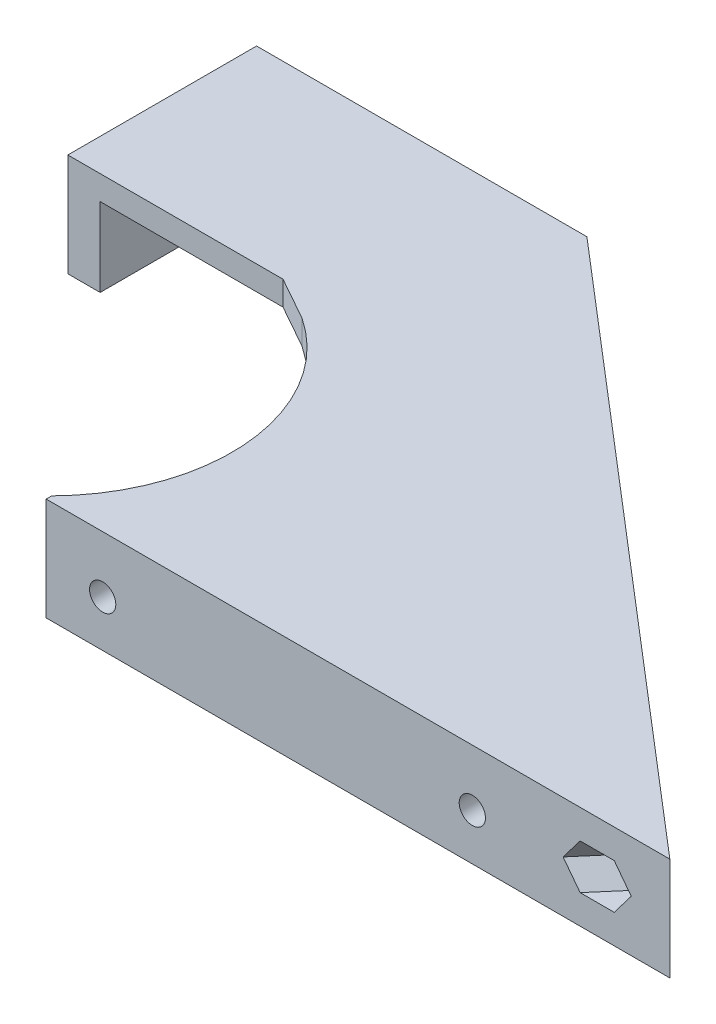
SolidWorks part; units mm, degrees
ref_plane "Alzado" through (0, 0, 0) normal (0, 0, 1) x (1, 0, 0)
ref_plane "Planta" through (0, 0, 0) normal (0, 1, 0) x (1, 0, 0)
ref_plane "Vista lateral" through (0, 0, 0) normal (1, 0, 0) x (0, 0, -1)
sketch "Croquis1" plane through (0, 0, 0) normal (0, 1, 0) x (1, 0, 0)
  line L0 (0, 0) -> (72.7832, 0)
  line L1 (72.7832, 0) -> (38.2245, 29.6204)
  line L2 (38.2245, 29.6204) -> (35.6214, 26.5833)
  line L3 (35.6214, 26.5833) -> (60.8031, 5)
  line L4 (60.8031, 5) -> (0, 5)
  line L5 (0, 5) -> (0, 0)
  dimension "D1" = 4
  dimension "D2" = 5
  dimension "D3" = 40.6
  dimension "D4" = 72.7832
extrude "Saliente-Extruir1" add sketch "Croquis1" along normal blind 12.75
sketch "Croquis2" plane through (0, 0, 0) normal (0, 0, 1) x (1, 0, 0)
  line L2 (0, 12.75) -> (72.7832, 12.75) construction
  line L3 (72.7832, 12.75) -> (72.7832, 0) construction
  circle A0 centre (52.7832, 5.75) radius 1.625
  circle A1 centre (7, 5.75) radius 1.625
  dimension "D1" = 3.25
  dimension "D2" = 20
  dimension "D3" = 7
  dimension "D4" = 45.7832
  dimension "D5" = 7
extrude "Cortar-Extruir1" cut sketch "Croquis2" against normal up to next
sketch "Croquis3" plane through (0, 12.75, 0) normal (0, 1, 0) x (1, 0, 0)
  line L0 (0, 5) -> (0, 0) construction
  line L1 (0, 0) -> (72.7832, 0) construction
  circle A0 centre (-16, 16.5) radius 22.5
  dimension "D1" = 45
  dimension "D2" = 16
  dimension "D3" = 16.5
extrude "Cortar-Extruir2" cut sketch "Croquis3" against normal through all
sketch "Croquis4" plane through (0, 12.75, 0) normal (0, 1, 0) x (1, 0, 0)
  line L0 (38.2245, 29.6204) -> (31.6563, 35.25)
  line L1 (31.6563, 35.25) -> (-3.5627, 35.25)
  line L2 (0, 0) -> (72.7832, 0) construction
  line L3 (72.7832, 0) -> (38.2245, 29.6204) construction
  line L4 (38.2245, 29.6204) -> (35.6214, 26.5833)
  line L5 (35.6214, 26.5833) -> (60.8031, 5)
  line L6 (60.8031, 5) -> (3.3391, 5)
  arc A0 (3.3391, 5) -> (-3.5627, 35.25) centre (-16, 16.5) ccw
  arc A1 (0, 0.6807) -> (3.3391, 5) centre (-16, 16.5) ccw construction
  dimension "D1" = 35.25
extrude "Saliente-Extruir2" add sketch "Croquis4" against normal blind 3
sketch "Croquis5" plane through (0, 9.75, 0) normal (0, -1, 0) x (1, 0, 0)
  line L0 (-3.5627, -35.25) -> (31.6563, -35.25)
  line L1 (31.6563, -35.25) -> (38.2245, -29.6204)
  line L2 (38.2245, -29.6204) -> (35.6214, -26.5833)
  line L3 (35.6214, -26.5833) -> (30.1767, -31.25)
  line L4 (30.1767, -31.25) -> (0.9908, -31.25)
  arc A0 (-3.5627, -35.25) -> (3.3391, -5) centre (-16, -16.5) ccw construction
  arc A1 (-3.5627, -35.25) -> (0.9908, -31.25) centre (-16, -16.5) ccw
  dimension "D1" = 4
extrude "Saliente-Extruir3" add sketch "Croquis5" along normal up to vertex (9.75 mm away) up to point (38.2245, 0, -29.6204)
sketch "Croquis6" plane through (30.8242, 0, -35.9632) normal (0.6508, 0, -0.7593) x (-0.7593, 0, -0.6508)
  line L0 (-55.2622, 12.75) -> (-55.2622, 0) construction
  line L1 (-1.0959, 0) -> (-1.0959, 12.75) construction
  circle A0 centre (-47.2622, 6.375) radius 1.625
  circle A1 centre (-16.0959, 6.375) radius 1.625
  dimension "D1" = 3.25
  dimension "D2" = 3.25
  dimension "D3" = 8
  dimension "D4" = 15
extrude "Cortar-Extruir3" cut sketch "Croquis6" against normal blind 10
sketch "Croquis7" plane through (28.2211, 0, -32.9261) normal (-0.6508, 0, 0.7593) x (0.7593, 0, 0.6508)
  line L1 (48.8499, 3.625) -> (50.4376, 6.375)
  line L2 (50.4376, 6.375) -> (48.8499, 9.125)
  line L3 (48.8499, 9.125) -> (45.6745, 9.125)
  line L4 (45.6745, 9.125) -> (44.0868, 6.375)
  line L5 (44.0868, 6.375) -> (45.6745, 3.625)
  line L6 (45.6745, 3.625) -> (48.8499, 3.625)
  circle A0 centre (47.2622, 6.375) radius 2.75 construction
  dimension "D1" = 5.5
extrude "Cortar-Extruir4" cut sketch "Croquis7" along normal blind 10 from offset 2 offset against normal yes
sketch "Croquis8" plane through (28.2211, 0, -32.9261) normal (-0.6508, 0, 0.7593) x (0.7593, 0, 0.6508)
  line L0 (45.6745, 3.625) -> (48.8499, 3.625) construction
  line L1 (17.6837, 3.625) -> (19.2714, 6.375)
  line L2 (19.2714, 6.375) -> (17.6837, 9.125)
  line L3 (17.6837, 9.125) -> (14.5082, 9.125)
  line L4 (14.5082, 9.125) -> (12.9205, 6.375)
  line L5 (12.9205, 6.375) -> (14.5082, 3.625)
  line L6 (14.5082, 3.625) -> (17.6837, 3.625)
  circle A0 centre (16.0959, 6.375) radius 2.75 construction
extrude "Cortar-Extruir5" cut sketch "Croquis8" along normal blind 10 from offset 2 offset against normal yes
sketch "Croquis9" plane through (0, 0, -5) normal (0, 0, -1) x (-1, 0, 0)
  line L1 (-5.4123, 3) -> (-3.8246, 5.75)
  line L2 (-3.8246, 5.75) -> (-5.4123, 8.5)
  line L3 (-5.4123, 8.5) -> (-8.5877, 8.5)
  line L4 (-8.5877, 8.5) -> (-10.1754, 5.75)
  line L5 (-10.1754, 5.75) -> (-8.5877, 3)
  line L6 (-8.5877, 3) -> (-5.4123, 3)
  line L7 (-51.1955, 3) -> (-49.6078, 5.75)
  line L8 (-49.6078, 5.75) -> (-51.1955, 8.5)
  line L9 (-51.1955, 8.5) -> (-54.3709, 8.5)
  line L10 (-54.3709, 8.5) -> (-55.9586, 5.75)
  line L11 (-55.9586, 5.75) -> (-54.3709, 3)
  line L12 (-54.3709, 3) -> (-51.1955, 3)
  circle A0 centre (-7, 5.75) radius 2.75 construction
  circle A1 centre (-52.7832, 5.75) radius 2.75 construction
  dimension "D1" = 5.5
extrude "Cortar-Extruir6" cut sketch "Croquis9" against normal blind 2
sketch "Croquis10" plane through (0, 0, -35.25) normal (0, 0, -1) x (-1, 0, 0)
  line L0 (-31.6563, 0) -> (-31.6563, 12.75) construction
  circle A0 centre (-21.6563, 6.375) radius 1.625
  dimension "D1" = 3.25
  dimension "D2" = 10
extrude "Cortar-Extruir7" cut sketch "Croquis10" against normal up to next
sketch "Croquis11" plane through (0, 0, -31.25) normal (0, 0, 1) x (1, 0, 0)
  line L1 (23.244, 3.625) -> (24.8317, 6.375)
  line L2 (24.8317, 6.375) -> (23.244, 9.125)
  line L3 (23.244, 9.125) -> (20.0686, 9.125)
  line L4 (20.0686, 9.125) -> (18.4809, 6.375)
  line L5 (18.4809, 6.375) -> (20.0686, 3.625)
  line L6 (20.0686, 3.625) -> (23.244, 3.625)
  circle A0 centre (21.6563, 6.375) radius 2.75 construction
  dimension "D1" = 5.5
extrude "Cortar-Extruir8" cut sketch "Croquis11" against normal blind 2
mirror "Simetría1" about plane through (0, 0, 0) normal (0, 1, 0) of bodies 111
sketch "Croquis12" plane through (0, 0, -35.25) normal (0, 0, -1) x (-1, 0, 0)
  line L1 (-79.3319, 0) -> (13.1768, 0)
  line L2 (-79.3319, 0) -> (-79.3319, 24.2558)
  line L3 (-79.3319, 24.2558) -> (13.1768, 24.2558)
  line L4 (13.1768, 0) -> (13.1768, 24.2558)
extrude "Cortar-Extruir9" cut sketch "Croquis12" against normal through all both and the other way through all
sketch "Croquis13" plane through (0, -12.75, 0) normal (0, -1, 0) x (1, 0, 0)
  line L1 (-35.5627, -82.3826) -> (-35.5627, -38.25)
  line L3 (-3.5627, -35.25) -> (31.6563, -35.25)
  line L5 (31.6563, -35.25) -> (0.0002, -62.3826)
  line L6 (0.0002, -62.3826) -> (-35.5627, -82.3826)
  line L7 (72.7832, 0) -> (31.6563, -35.25) construction
  line L8 (-3.5627, -35.25) -> (-8.9133, -38.25)
  line L9 (-8.9133, -38.25) -> (-35.5627, -38.25)
  dimension "D1" = 32
  dimension "D2" = 3
  dimension "D3" = 20
extrude "Saliente-Extruir4" add sketch "Croquis13" against normal up to vertex (12.75 mm away) up to point (31.6563, 0, -35.25)
sketch "Croquis14" plane through (0, 0, 0) normal (0, 1, 0) x (1, 0, 0)
  line L3 (30.1767, 31.25) -> (0.9908, 31.25)
  line L4 (0.9908, 31.25) -> (-31.5627, 38.25)
  line L6 (-31.5627, 38.25) -> (-31.5627, 75.5439)
  line L7 (-2.3039, 59.0892) -> (70.1801, -3.0371)
  line L8 (-31.5627, 75.5439) -> (-2.3039, 59.0892)
  line L9 (-31.5627, 38.25) -> (-31.5627, 75.5439)
  line L10 (-2.3039, 59.0892) -> (30.1767, 31.25)
  line L11 (-31.5627, 75.5439) -> (-2.3039, 59.0892)
  dimension "D1" = 4
extrude "Cortar-Extruir10" cut sketch "Croquis14" against normal up to vertex (9.75 mm away) up to point (0.9908, -9.75, -31.25)
sketch "Croquis16" plane through (30.8242, 0, -35.9632) normal (0.6508, 0, -0.7593) x (-0.7593, 0, -0.6508)
  line L0 (40.5969, 0) -> (-55.2622, 0) construction
  line L1 (-36.0959, 0) -> (40.5969, 0)
  line L2 (-36.0959, 0) -> (-36.0959, -12.75)
  line L3 (-36.0959, -12.75) -> (40.5969, -12.75)
  line L4 (40.5969, 0) -> (40.5969, -12.75)
  circle A0 centre (-16.0959, -6.375) radius 1.625 construction
  dimension "D1" = 20
  dimension "D2" = 76.6928
extrude "Cortar-Extruir11" cut sketch "Croquis16" against normal blind 1
sketch "Croquis17" plane through (0, -12.75, 0) normal (0, -1, 0) x (1, 0, 0)
  line L1 (0.0002, -61.6233) -> (-40.6573, -61.6233)
  line L2 (0.0002, -61.6233) -> (0.0002, -84.5579)
  line L3 (0.0002, -84.5579) -> (-40.6573, -84.5579)
  line L4 (-40.6573, -61.6233) -> (-40.6573, -84.5579)
extrude "Cortar-Extruir12" cut sketch "Croquis17" against normal through all both and the other way through all
sketch "Croquis18" plane through (0, 0, 0) normal (0, 1, 0) x (1, 0, 0)
  line L0 (60.8031, 5) -> (-2.3039, 59.0892) construction
  line L1 (-35.5627, 61.6233) -> (-0.6506, 61.6233)
  line L2 (-35.5627, 61.6233) -> (-35.5627, 57.6722)
  line L3 (-35.5627, 57.6722) -> (-0.6506, 57.6722)
  line L4 (-0.6506, 61.6233) -> (-0.6506, 57.6722)
extrude "Saliente-Extruir5" add sketch "Croquis18" against normal up to surface (9.75 mm away)
sketch "Croquis20" plane through (30.1734, 0, -35.2039) normal (0.6508, 0, -0.7593) x (-0.7593, 0, -0.6508)
  line L2 (40.5969, -12.75) -> (40.5969, 0) construction
  circle A0 centre (25.5969, -6.375) radius 1.625
  circle A1 centre (-16.0959, -6.375) radius 1.625 construction
  circle A2 centre (-16.0959, -6.375) radius 1.625
  dimension "D2" = 41.6928
  dimension "D1" = 15
extrude "Cortar-Extruir14" cut sketch "Croquis20" against normal blind 10
sketch "Croquis21" plane through (28.2211, 0, -32.9261) normal (-0.6508, 0, 0.7593) x (0.7593, 0, 0.6508)
  line L0 (17.6837, -9.125) -> (14.5082, -9.125) construction
  line L1 (-24.0092, -9.125) -> (-22.4214, -6.375)
  line L2 (-22.4214, -6.375) -> (-24.0092, -3.625)
  line L3 (-24.0092, -3.625) -> (-27.1846, -3.625)
  line L4 (-27.1846, -3.625) -> (-28.7723, -6.375)
  line L5 (-28.7723, -6.375) -> (-27.1846, -9.125)
  line L6 (-27.1846, -9.125) -> (-24.0092, -9.125)
  circle A0 centre (-25.5969, -6.375) radius 2.75 construction
extrude "Cortar-Extruir15" cut sketch "Croquis21" against normal up to vertex (2 mm away) up to point (42.9493, -9.125, -22.9366)
sketch "Croquis22" plane through (0, 0, -61.6233) normal (0, 0, -1) x (-1, 0, 0)
  line L0 (35.5627, -12.75) -> (35.5627, 0) construction
  circle A0 centre (18.1127, -6.375) radius 1.625
  dimension "D1" = 3.25
  dimension "D2" = 17.45
extrude "Cortar-Extruir16" cut sketch "Croquis22" against normal blind 10
sketch "Croquis23" plane through (0, 0, -57.6722) normal (0, 0, 1) x (1, 0, 0)
  line L0 (7.5806, -9.125) -> (9.9916, -9.125) construction
  line L1 (-16.5249, -9.125) -> (-14.9372, -6.375)
  line L2 (-14.9372, -6.375) -> (-16.5249, -3.625)
  line L3 (-16.5249, -3.625) -> (-19.7004, -3.625)
  line L4 (-19.7004, -3.625) -> (-21.2881, -6.375)
  line L5 (-21.2881, -6.375) -> (-19.7004, -9.125)
  line L6 (-19.7004, -9.125) -> (-16.5249, -9.125)
  circle A0 centre (-18.1127, -6.375) radius 2.75 construction
extrude "Cortar-Extruir17" cut sketch "Croquis23" against normal blind 2
sketch "Croquis26" plane through (0, 0, 0) normal (0, 1, 0) x (1, 0, 0)
  line L0 (60.8031, 5) -> (-2.2878, 59.0754)
  line L1 (60.8031, 5) -> (60.1523, 4.2407)
  line L2 (-2.2878, 59.0754) -> (-2.9386, 58.3161)
  line L3 (60.1523, 4.2407) -> (-2.9386, 58.3161)
  line L5 (60.8031, 5) -> (-0.6506, 57.6722) construction
  dimension "D1" = 1
extrude "Saliente-Extruir6" add sketch "Croquis26" against normal up to vertex (12.75 mm away) up to point (-0.6506, -12.75, -61.6233)
sketch "Croquis27" plane through (27.5703, 0, -32.1669) normal (-0.6508, 0, 0.7593) x (0.7593, 0, 0.6508)
  line L1 (-22.4214, -6.375) -> (-24.0092, -3.625)
  line L2 (-24.0092, -3.625) -> (-27.1846, -3.625)
  line L3 (-27.1846, -3.625) -> (-28.7723, -6.375)
  line L4 (-28.7723, -6.375) -> (-27.1846, -9.125)
  line L5 (-27.1846, -9.125) -> (-24.0092, -9.125)
  line L6 (-24.0092, -9.125) -> (-22.4214, -6.375)
  line L7 (19.2714, -6.375) -> (17.6837, -3.625)
  line L8 (17.6837, -3.625) -> (14.5082, -3.625)
  line L9 (14.5082, -3.625) -> (12.9205, -6.375)
  line L10 (12.9205, -6.375) -> (14.5082, -9.125)
  line L11 (14.5082, -9.125) -> (17.6837, -9.125)
  line L12 (17.6837, -9.125) -> (19.2714, -6.375)
  circle A0 centre (-25.5969, -6.375) radius 2.75 construction
  circle A1 centre (16.0959, -6.375) radius 2.75 construction
extrude "Cortar-Extruir18" cut sketch "Croquis27" against normal blind 2
sketch "Croquis28" plane through (29.5227, 0, -34.4447) normal (-0.6508, 0, 0.7593) x (0.7593, 0, 0.6508)
  line L1 (-24.0092, -3.625) -> (-27.1846, -3.625)
  line L2 (-27.1846, -3.625) -> (-28.7723, -6.375)
  line L3 (-28.7723, -6.375) -> (-27.1846, -9.125)
  line L4 (-27.1846, -9.125) -> (-24.0092, -9.125)
  line L5 (-24.0092, -9.125) -> (-22.4214, -6.375)
  line L6 (-22.4214, -6.375) -> (-24.0092, -3.625)
  line L7 (17.6837, -3.625) -> (14.5082, -3.625)
  line L8 (14.5082, -3.625) -> (12.9205, -6.375)
  line L9 (12.9205, -6.375) -> (14.5082, -9.125)
  line L10 (14.5082, -9.125) -> (17.6837, -9.125)
  line L11 (17.6837, -9.125) -> (19.2714, -6.375)
  line L12 (19.2714, -6.375) -> (17.6837, -3.625)
  circle A0 centre (-25.5969, -6.375) radius 2.75 construction
  circle A1 centre (16.0959, -6.375) radius 2.75 construction
  circle A2 centre (-25.5969, -6.375) radius 1.625
  circle A3 centre (16.0959, -6.375) radius 1.625
extrude "Saliente-Extruir7" add sketch "Croquis28" along normal blind 1
sketch "Croquis29" plane through (-35.5627, 0, 0) normal (-1, 0, 0) x (0, 0, 1)
  line L0 (-61.6233, -12.75) -> (-61.6233, 0) construction
  line L1 (-38.25, 0) -> (-61.6233, 0) construction
  circle A0 centre (-51.6233, -6.375) radius 1.9933
  dimension "D1" = 10
  dimension "D2" = 6.375
extrude "Cortar-Extruir19" cut sketch "Croquis29" against normal up to next
sketch "Croquis30" plane through (-31.5627, 0, 0) normal (1, 0, 0) x (0, 0, -1)
  line L0 (52.4097, -6.375) -> (50.8911, -6.375) construction
  line L1 (53.2381, -9.125) -> (54.8258, -6.375)
  line L2 (54.8258, -6.375) -> (53.2381, -3.625)
  line L3 (53.2381, -3.625) -> (50.0627, -3.625)
  line L4 (50.0627, -3.625) -> (48.475, -6.375)
  line L5 (48.475, -6.375) -> (50.0627, -9.125)
  line L6 (50.0627, -9.125) -> (53.2381, -9.125)
  circle A0 centre (51.6504, -6.375) radius 2.75 construction
  dimension "D1" = 5.5
extrude "Cortar-Extruir20" cut sketch "Croquis30" against normal blind 2
sketch "Croquis32" plane through (0, -12.75, 0) normal (0, -1, 0) x (1, 0, 0)
  line L0 (-0.6506, -61.6233) -> (5.3494, -61.6233)
  line L1 (5.3494, -61.6233) -> (60.1211, -14.6783)
  line L2 (60.1211, -14.6783) -> (60.7719, -15.4376)
  line L3 (60.7719, -15.4376) -> (78.7832, 0)
  line L4 (78.7832, 0) -> (72.7832, 0)
  line L5 (72.7832, 0) -> (58.2308, -12.4729)
  line L6 (58.2308, -12.4729) -> (57.58, -11.7136)
  line L7 (57.58, -11.7136) -> (-0.6506, -61.6233)
  dimension "D1" = 6
  dimension "D2" = 3.9046
  dimension "D3" = 1
extrude "Saliente-Extruir8" add sketch "Croquis32" against normal up to vertex (12.75 mm away) up to point (-0.6506, 0, -61.6233)
sketch "Croquis33" plane through (32.7145, 0, -38.1686) normal (0.6508, 0, -0.7593) x (-0.7593, 0, -0.6508)
  line L1 (-14.5082, -3.625) -> (-17.6837, -3.625)
  line L2 (-17.6837, -3.625) -> (-19.2714, -6.375)
  line L3 (-19.2714, -6.375) -> (-17.6837, -9.125)
  line L4 (-17.6837, -9.125) -> (-14.5082, -9.125)
  line L5 (-14.5082, -9.125) -> (-12.9205, -6.375)
  line L6 (-12.9205, -6.375) -> (-14.5082, -3.625)
  line L7 (27.1846, -3.625) -> (24.0092, -3.625)
  line L8 (24.0092, -3.625) -> (22.4214, -6.375)
  line L9 (22.4214, -6.375) -> (24.0092, -9.125)
  line L10 (24.0092, -9.125) -> (27.1846, -9.125)
  line L11 (27.1846, -9.125) -> (28.7723, -6.375)
  line L12 (28.7723, -6.375) -> (27.1846, -3.625)
  circle A0 centre (-16.0959, -6.375) radius 2.75 construction
  circle A1 centre (25.5969, -6.375) radius 2.75 construction
extrude "Saliente-Extruir9" add sketch "Croquis33" along normal blind 5 from vertex starting at point (42.2025, -6.375, -19.6255)
sketch "Croquis34" plane through (33.3652, 0, -38.9279) normal (0.6508, 0, -0.7593) x (-0.7593, 0, -0.6508)
  line L1 (-45.6745, -3.625) -> (-48.8499, -3.625)
  line L2 (-48.8499, -3.625) -> (-50.4376, -6.375)
  line L3 (-50.4376, -6.375) -> (-48.8499, -9.125)
  line L4 (-48.8499, -9.125) -> (-45.6745, -9.125)
  line L5 (-45.6745, -9.125) -> (-44.0868, -6.375)
  line L6 (-44.0868, -6.375) -> (-45.6745, -3.625)
  circle A0 centre (-47.2622, -6.375) radius 2.75 construction
extrude "Saliente-Extruir10" add sketch "Croquis34" against normal up to surface (12.1223 mm away) up to face at (39.3916, -6.375, 0)
sketch "Croquis35" plane through (0, 0, 0) normal (0, 1, 0) x (1, 0, 0)
  line L0 (-2.1872, 57.6722) -> (3.8128, 57.6722)
  line L1 (3.8128, 57.6722) -> (65.2664, 5)
  line L2 (65.2664, 5) -> (59.2664, 5)
  line L3 (59.2664, 5) -> (-2.1872, 57.6722)
  line L4 (5.3494, 61.6233) -> (60.1211, 14.6783) construction
  line L5 (3.3391, 5) -> (59.2664, 5) construction
  dimension "D1" = 6
extrude "Cortar-Extruir21" cut sketch "Croquis35" against normal up to surface (9.75 mm away)
sketch "Croquis36" plane through (33.3652, 0, -38.9279) normal (0.6508, 0, -0.7593) x (-0.7593, 0, -0.6508)
  line L0 (-59.8178, 0) -> (-59.8178, -12.75) construction
  line L1 (-36.0959, 0) -> (-59.8178, 0) construction
  circle A0 centre (-51.8178, -6.375) radius 1.625
  circle A1 centre (-20.6478, -6.375) radius 1.625
  circle A2 centre (21.0422, -6.375) radius 1.625
  dimension "D1" = 3.25
  dimension "D3" = 31.17
  dimension "D4" = 41.69
  dimension "D5" = 6.375
  dimension "D2" = 8
extrude "Cortar-Extruir22" cut sketch "Croquis36" against normal blind 15
sketch "Croquis38" plane through (30.1114, 0, -35.1315) normal (-0.6508, 0, 0.7593) x (0.7593, 0, 0.6508)
  line L1 (-19.44, -9.15) -> (-17.8379, -6.375)
  line L2 (-17.8379, -6.375) -> (-19.44, -3.6)
  line L3 (-19.44, -3.6) -> (-22.6443, -3.6)
  line L4 (-22.6443, -3.6) -> (-24.2465, -6.375)
  line L5 (-24.2465, -6.375) -> (-22.6443, -9.15)
  line L6 (-22.6443, -9.15) -> (-19.44, -9.15)
  line L7 (22.25, -9.15) -> (23.8521, -6.375)
  line L8 (23.8521, -6.375) -> (22.25, -3.6)
  line L9 (22.25, -3.6) -> (19.0457, -3.6)
  line L10 (19.0457, -3.6) -> (17.4435, -6.375)
  line L11 (17.4435, -6.375) -> (19.0457, -9.15)
  line L12 (19.0457, -9.15) -> (22.25, -9.15)
  circle A0 centre (-21.0422, -6.375) radius 2.775 construction
  circle A1 centre (20.6478, -6.375) radius 2.775 construction
  dimension "D1" = 5.55
extrude "Cortar-Extruir23" cut sketch "Croquis38" against normal blind 2
sketch "Croquis39" plane through (33.3652, 0, -38.9279) normal (0.6508, 0, -0.7593) x (-0.7593, 0, -0.6508)
  line L1 (-50.2157, -9.15) -> (-48.6135, -6.375)
  line L2 (-48.6135, -6.375) -> (-50.2157, -3.6)
  line L3 (-50.2157, -3.6) -> (-53.42, -3.6)
  line L4 (-53.42, -3.6) -> (-55.0221, -6.375)
  line L5 (-55.0221, -6.375) -> (-53.42, -9.15)
  line L6 (-53.42, -9.15) -> (-50.2157, -9.15)
  circle A0 centre (-51.8178, -6.375) radius 2.775 construction
  dimension "D1" = 5.55
extrude "Cortar-Extruir24" cut sketch "Croquis39" against normal through all from offset 2 offset against normal yes
mirror "Simetría2" of bodies 136 118
sketch "Croquis19" plane through (0, 0, -61.6233) normal (0, 0, -1) x (-1, 0, 0)
  line L1 (-78.7832, -12.75) -> (41.6655, -12.75)
  line L2 (-78.7832, -12.75) -> (-78.7832, 20.1367)
  line L3 (-78.7832, 20.1367) -> (41.6655, 20.1367)
  line L4 (41.6655, -12.75) -> (41.6655, 20.1367)
  line L5 (-78.7832, 0) -> (-78.7832, -25.5) construction
extrude "Cortar-Extruir13" cut sketch "Croquis19" against normal through all both and the other way through all
sketch "Croquis40" plane through (0, -25.5, 0) normal (0, -1, 0) x (1, 0, 0)
  line L0 (60.1211, -14.6783) -> (60.7719, -15.4376)
  line L1 (60.1211, -14.6783) -> (81.2695, 3.4481)
  line L2 (60.7719, -15.4376) -> (81.9203, 2.6888)
  line L3 (81.2695, 3.4481) -> (81.9203, 2.6888)
extrude "Cortar-Extruir25" cut sketch "Croquis40" against normal through all both and the other way through all
sketch "Croquis42" plane through (32.0637, 0, -37.4094) normal (-0.6508, 0, 0.7593) x (0.7593, 0, 0.6508)
  line L1 (53.42, -16.35) -> (50.2157, -16.35)
  line L2 (50.2157, -16.35) -> (48.6135, -19.125)
  line L3 (48.6135, -19.125) -> (50.2157, -21.9)
  line L4 (50.2157, -21.9) -> (53.42, -21.9)
  line L5 (53.42, -21.9) -> (55.0221, -19.125)
  line L6 (55.0221, -19.125) -> (53.42, -16.35)
  circle A0 centre (51.8178, -19.125) radius 1.625
  circle A1 centre (51.8178, -19.125) radius 2.775 construction
extrude "Saliente-Extruir11" add sketch "Croquis42" along normal blind 1
